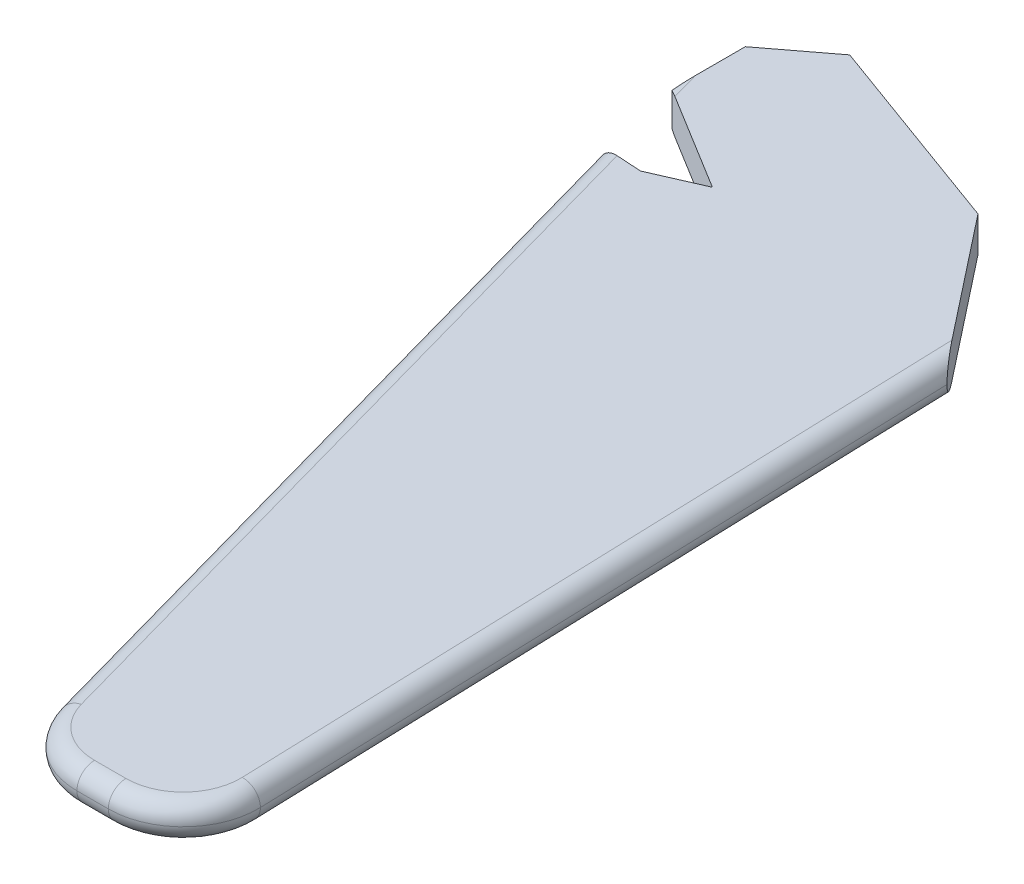
SolidWorks part; units mm, degrees
ref_plane "Front Plane" through (0, 0, 0) normal (0, 0, 1) x (1, 0, 0)
ref_plane "Top Plane" through (0, 0, 0) normal (0, 1, 0) x (1, 0, 0)
ref_plane "Right Plane" through (0, 0, 0) normal (1, 0, 0) x (0, 0, -1)
sketch "Sketch2" plane through (0, 0, 0) normal (0, 1, 0) x (1, 0, 0)
  line L0 (-19.4447, 54.4598) -> (-19.4447, 28.4598)
  line L1 (-19.4447, 28.4598) -> (5.6021, -61.3687)
  line L2 (13.7897, -67.5857) -> (17.3593, -67.5857)
  line L3 (25.8548, -58.8098) -> (22.1771, 54.4395)
  line L5 (22.803, 54.4598) -> (-19.4447, 54.4598)
  line L6 (-53.3587, 51.9865) -> (24.4322, 54.5127) construction
  line L7 (22.803, 54.4598) -> (22.1771, 54.4395)
  arc A1 (17.3593, -67.5857) -> (25.8548, -58.8098) centre (17.3593, -59.0857) ccw
  arc A2 (5.6021, -61.3687) -> (13.7897, -67.5857) centre (13.7897, -59.0857) ccw
  dimension "D2" = 8.5
  dimension "D3" = 8.5
  dimension "D5" = 26
extrude "Boss-Extrude1" add sketch "Sketch2" along normal blind 4 contours L3 L7 L5 L0 L1 A2 L2 A1
fillet "Fillet5" radius 2 11 edges at (24.016, 4, 2.1852) (23.4665, 4, 64.9978) (15.5745, 4, 67.5857) (8.6495, 4, 65.8553) (24.016, 0, 2.1852) (23.4665, 0, 64.9978) (15.5745, 0, 67.5857) (8.6495, 0, 65.8553) (-19.4447, 2, -28.4598) (-6.9213, 4, 16.4545) (-6.9213, 0, 16.4545)
sketch "Sketch3" plane through (0, 0, 0) normal (0, -1, 0) x (1, 0, 0)
  circle A0 centre (-9.8811, -35.0337) radius 4
extrude "Boss-Extrude2" add sketch "Sketch3" along normal blind 4
sketch "Sketch4" plane through (0, 4, 0) normal (0, 1, 0) x (1, 0, 0)
  line L0 (23.2374, 21.7899) -> (-2.479, 54.4598)
  line L1 (25.8548, -58.8098) -> (22.1771, 54.4395) construction
  line L2 (22.803, 54.4598) -> (-19.4447, 54.4598) construction
  line L3 (-2.479, 54.4598) -> (-19.4447, 41.5661)
  line L4 (-19.4447, 54.4598) -> (-19.4447, 35.9063) construction
  line L5 (-19.4447, 41.5661) -> (-32.3231, 58.5116)
  line L6 (-32.3231, 58.5116) -> (23.2374, 102.2465)
  line L7 (23.2374, 102.2465) -> (62.3405, 52.5702)
  line L8 (62.3405, 52.5702) -> (23.2374, 21.7899)
extrude "Cut-Extrude1" cut sketch "Sketch4" against normal up to next
sketch "Sketch5" plane through (0, 4, 0) normal (0, 1, 0) x (1, 0, 0)
  line L0 (10.2163, 38.3318) -> (-12.7075, 46.6863)
  line L1 (-2.479, 54.4598) -> (21.1502, 24.4414) construction
  line L2 (-12.7075, 46.6863) -> (-5.2747, 62.107)
  line L3 (-5.2747, 62.107) -> (10.2163, 38.3318)
  line L4 (-19.4447, 33.2217) -> (-7.4864, 25.8694)
  line L5 (-19.4447, 35.9063) -> (-19.4447, 28.7334) construction
  line L6 (-7.4864, 25.8694) -> (-13.1676, 23.3865)
  line L8 (-13.1676, 23.3865) -> (-19.943, 23.8073)
  line L9 (-19.943, 23.8073) -> (-19.4447, 33.2217)
  line L11 (-19.4447, 41.5661) -> (-2.479, 54.4598) construction
extrude "Cut-Extrude2" cut sketch "Sketch5" against normal up to next
